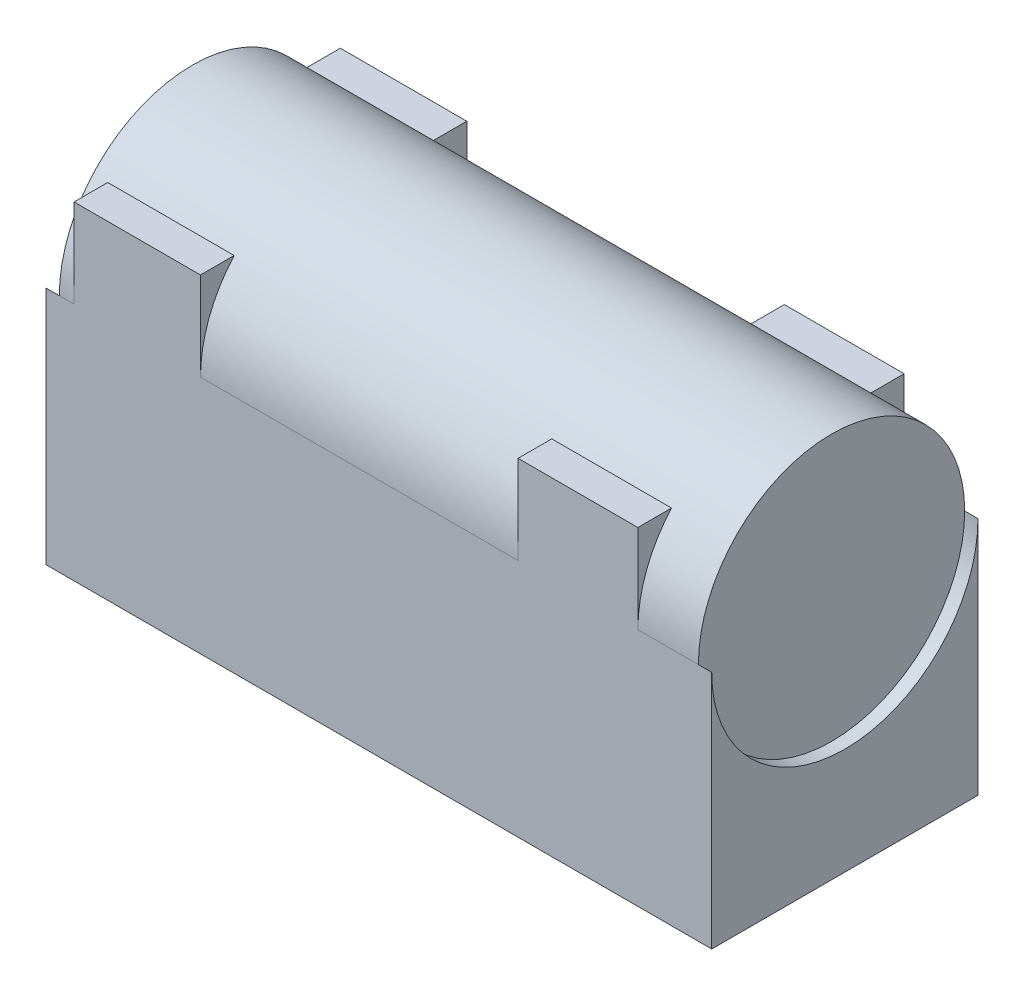
SolidWorks part; units mm, degrees
ref_plane "Front Plane" through (0, 0, 0) normal (0, 0, 1) x (1, 0, 0)
ref_plane "Top Plane" through (0, 0, 0) normal (0, 1, 0) x (1, 0, 0)
ref_plane "Right Plane" through (0, 0, 0) normal (1, 0, 0) x (0, 0, -1)
sketch "Sketch1" plane through (0, 0, 0) normal (1, 0, 0) x (0, 0, -1)
  line L0 (5, 0) -> (-5, 0)
  line L1 (-5, 0) -> (-5, 3)
  line L2 (-5, 3) -> (-5, 9)
  line L3 (0, 4.1818) -> (0, 0)
  line L4 (5, 0) -> (5, 3)
  line L5 (5, 3) -> (5, 9)
  arc A0 (-5, 9) -> (5, 9) centre (0, 9) ccw
  circle A1 centre (0, 9) radius 5
  dimension "D1" = 10
  dimension "D2" = 3
  dimension "D3" = 6
extrude "Boss-Extrude1" add sketch "Sketch1" along normal mid plane 25 contours L0 L1 L2 A0 L5 L4
extrude "Boss-Extrude2" add sketch "Sketch1<5>" along normal mid plane 24 contours A0 A1 region at (0, 9, 0)
sketch "Sketch1<5>" plane through (0, 0, 0) normal (1, 0, 0) x (0, 0, -1) same geometry as "Sketch1"
sketch "Sketch2" plane through (0, 0, 5) normal (0, 0, 1) x (1, 0, 0)
  line L0 (12, 9) -> (-12, 9) construction
  line L1 (-11.4471, 5.6762) -> (-6.6992, 5.6762)
  line L2 (-11.4471, 5.6762) -> (-11.4471, 12.3238)
  line L3 (-11.4471, 12.3238) -> (-6.6992, 12.3238)
  line L4 (-6.6992, 5.6762) -> (-6.6992, 12.3238)
  line L5 (-11.4471, 5.6762) -> (-6.6992, 12.3238) construction
  line L6 (-11.4471, 12.3238) -> (-6.6992, 5.6762) construction
  line L8 (5.2278, 12.3238) -> (9.727, 12.3238)
  line L9 (5.2278, 12.3238) -> (5.2278, 5.6762)
  line L10 (5.2278, 5.6762) -> (9.727, 5.6762)
  line L11 (9.727, 12.3238) -> (9.727, 5.6762)
  line L12 (5.2278, 12.3238) -> (9.727, 5.6762) construction
  line L13 (5.2278, 5.6762) -> (9.727, 12.3238) construction
  point P0 (-9.0732, 9)
  point P7 (7.4774, 9)
extrude "Boss-Extrude3" add sketch "Sketch2" against normal blind 10
